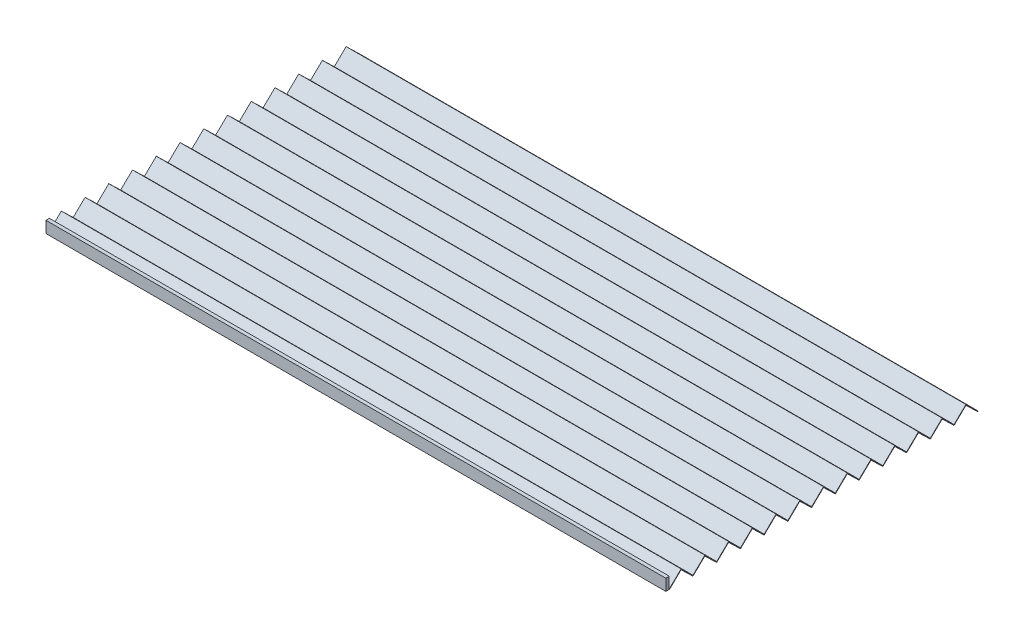
SolidWorks part; units mm, degrees
ref_plane "Front Plane" through (0, 0, 0) normal (0, 0, 1) x (1, 0, 0)
ref_plane "Top Plane" through (0, 0, 0) normal (0, 1, 0) x (1, 0, 0)
ref_plane "Right Plane" through (0, 0, 0) normal (1, 0, 0) x (0, 0, -1)
sketch "Sketch2" plane through (0, 0, 0) normal (0, 0, 1) x (1, 0, 0)
  line L1 (-270, 10) -> (270, 10)
  line L2 (-270, 10) -> (-270, 0)
  line L3 (-270, 0) -> (270, 0)
  line L4 (270, 10) -> (270, 0)
  point P4 (0, 0)
  dimension "D1" = 10
  dimension "D2" = 540
extrude "Boss-Extrude1" add sketch "Sketch2" along normal blind 3
sketch "Sketch3" plane through (270, 0, 0) normal (1, 0, 0) x (0, 0, -1)
  line L0 (0, 10) -> (268.8317, 10) construction
  line L1 (0, 0) -> (268.8317, 0) construction
  line L2 (268.8317, 10) -> (268.8317, 0) construction
  line L3 (0, 0) -> (10.3397, 10)
  line L4 (10.3397, 10) -> (20.6794, 0)
  line L5 (20.6794, 0) -> (31.019, 10)
  line L6 (31.019, 10) -> (41.3587, 0)
  line L7 (41.3587, 0) -> (51.6984, 10)
  line L8 (51.6984, 10) -> (62.0381, 0)
  line L9 (62.0381, 0) -> (72.3778, 10)
  line L10 (72.3778, 10) -> (82.7174, 0)
  line L11 (82.7174, 0) -> (93.0571, 10)
  line L12 (93.0571, 10) -> (103.3968, 0)
  line L13 (103.3968, 0) -> (113.7365, 10)
  line L14 (113.7365, 10) -> (124.0761, 0)
  line L15 (124.0761, 0) -> (134.4158, 10)
  line L16 (134.4158, 10) -> (144.7555, 0)
  line L17 (144.7555, 0) -> (155.0952, 10)
  line L18 (155.0952, 10) -> (165.4349, 0)
  line L20 (165.4349, 0) -> (175.7745, 10)
  line L21 (175.7745, 10) -> (186.1142, 0)
  line L22 (186.1142, 0) -> (196.4539, 10)
  line L23 (196.4539, 10) -> (206.7936, 0)
  line L24 (206.7936, 0) -> (217.1333, 10)
  line L25 (217.1333, 10) -> (227.4729, 0)
  line L26 (227.4729, 0) -> (237.8126, 10)
  line L27 (237.8126, 10) -> (248.1523, 0)
  line L28 (248.1523, 0) -> (258.492, 10)
  line L29 (258.492, 10) -> (268.8317, 0)
  line L30 (268.8317, 10) -> (268.8317, 0) construction
extrude "Extrude-Thin1" add sketch "Sketch3" against normal through all thin thin type mid plane wall 0.5
